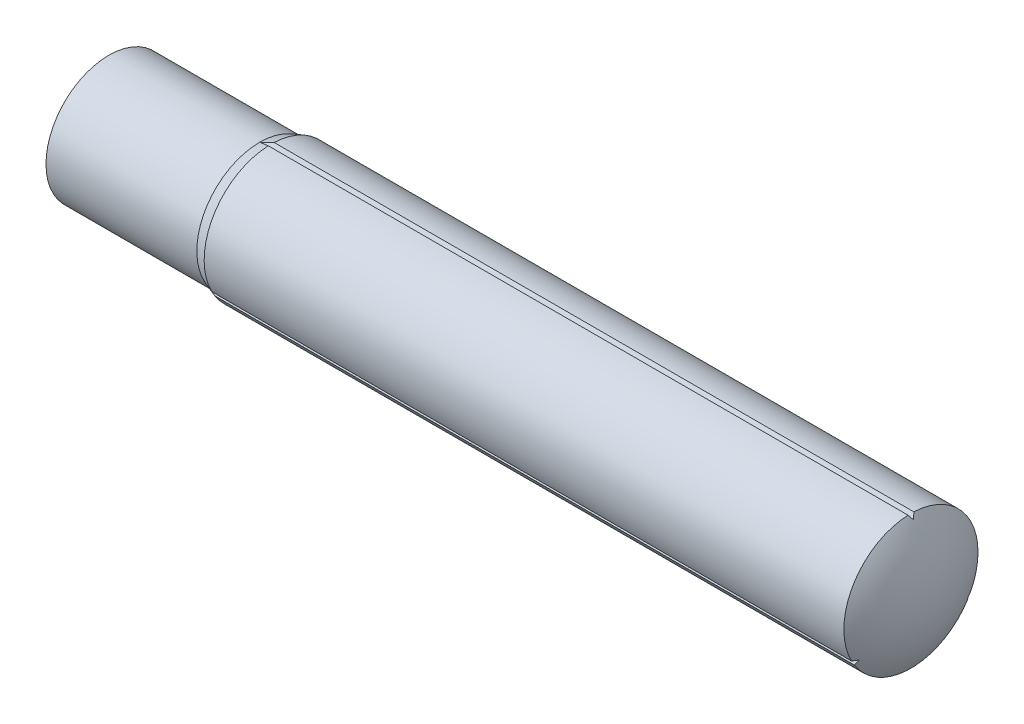
SolidWorks part; units mm, degrees
ref_plane "Front" through (0, 0, 0) normal (0, 0, 1) x (1, 0, 0)
ref_plane "Top" through (0, 0, 0) normal (0, 1, 0) x (1, 0, 0)
ref_plane "Right" through (0, 0, 0) normal (1, 0, 0) x (0, 0, -1)
sketch "Sketch1" plane through (0, 0, 0) normal (0, 0, 1) x (1, 0, 0)
  line L0 (0, 0) -> (10, 0)
  line L1 (-11.1634, 0) -> (0.7473, 0) construction
  line L3 (9.7689, 0.8) -> (2.1374, 0.8)
  line L4 (2.1374, 0.8) -> (2, 0.75)
  line L5 (2, 0.75) -> (0.201, 0.75)
  arc A0 (0.201, 0.75) -> (0, 0) centre (1.5, 0) ccw
  arc A1 (9.7689, 0.8) -> (10, 0) centre (8.5, 0) cw
  dimension "D7" = 20
  dimension "d2" = 1.6
revolve "Base-Revolve" add sketch "Sketch1" angle 360 about L1
sketch "Sketch5" plane through (0, 0, 0) normal (0, 0, 1) x (1, 0, 0)
  line L1 (2, 0.75) -> (0.201, 0.75)
  line L3 (2.1374, 0.8) -> (2, 0.75)
  line L4 (2.1374, 0.8) -> (0.2311, 0.8)
  line L6 (-10.4052, 0) -> (0.33, 0) construction
  line L8 (9.7689, 0.8) -> (2.1374, 0.8) construction
  line L9 (2, 0.75) -> (0.201, 0.75) construction
  arc A0 (0.201, 0.75) -> (0.201, -0.75) centre (1.5, 0) ccw construction
  arc A1 (0.2311, 0.8) -> (0.201, 0.75) centre (1.5, 0) ccw
revolve "Revolve1" [suppressed] add sketch "Sketch5" angle 360 about L6
sketch "Sketch2" plane through (0, 0, 0) normal (1, 0, 0) x (0, 0, -1)
  line L0 (-0.035, 0.8) -> (0, 0.75)
  line L1 (0, 0.75) -> (0.035, 0.8)
  line L2 (0.035, 0.8) -> (-0.035, 0.8)
  line L3 (0, 1.2136) -> (0, -0.2002) construction
  dimension "D1" = 70
  dimension "D2" = 35
  dimension "D3" = 0.8
  dimension "D4" = 0.75
extrude "Cut-Extrude1" cut sketch "Sketch2" along normal through all
pattern_circular "CirPattern1" count 3 over 360 about axis through (-11.1634, 0, 0) along (1, 0, 0) of "Cut-Extrude1"
equation "\"r@Sketch1\" = \"d@Sketch1\""
equation "\"r1@Sketch1\" = \"r@Sketch1\""
equation "\"D3@Sketch2\" = \"d2@Sketch1\" / 2"
equation "\"D4@Sketch2\" = \"d@Sketch1\" / 2"
